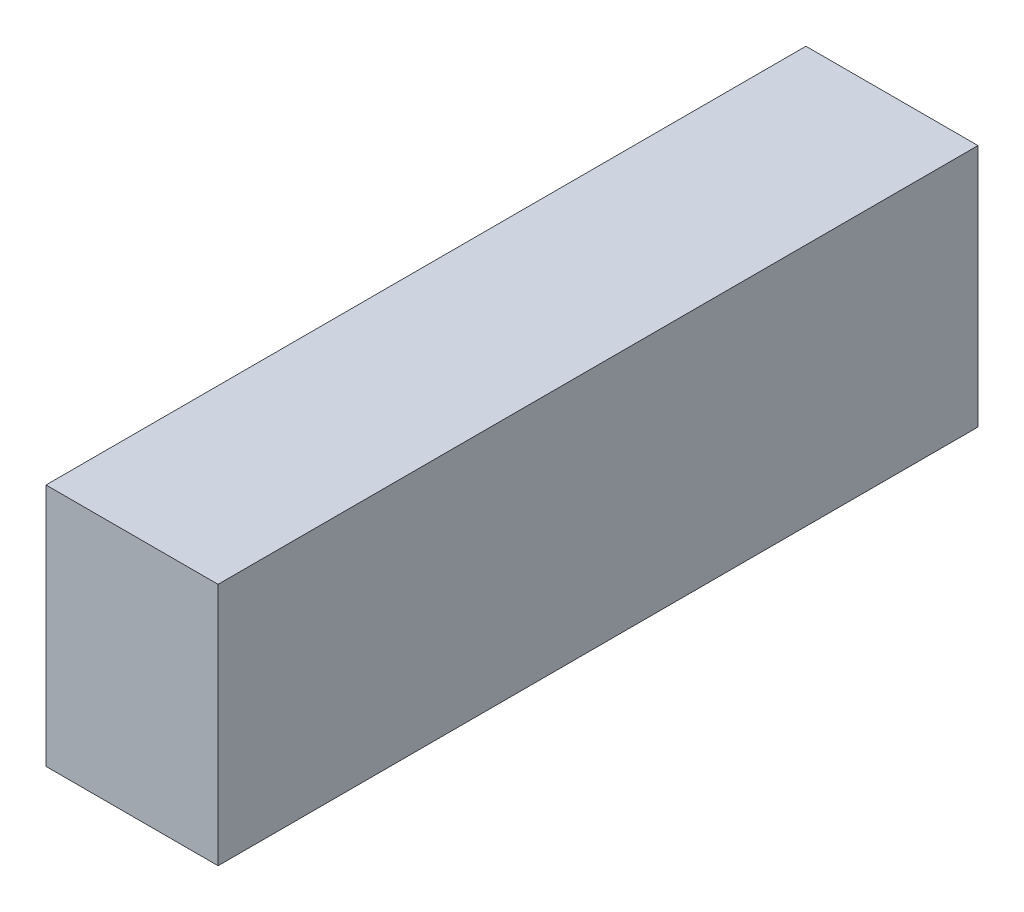
SolidWorks part; units mm, degrees
ref_plane "Front Plane" through (0, 0, 0) normal (0, 0, 1) x (1, 0, 0)
ref_plane "Top Plane" through (0, 0, 0) normal (0, 1, 0) x (1, 0, 0)
ref_plane "Right Plane" through (0, 0, 0) normal (1, 0, 0) x (0, 0, -1)
sketch "Case Sketch" plane through (0, 0, 0) normal (1, 0, 0) x (0, 0, -1)
  line L0 (53, 8) -> (53, 42)
  line L1 (53, 42) -> (-53, 42)
  line L2 (-53, 42) -> (-53, 8)
  line L3 (-53, 8) -> (53, 8)
extrude "Case" add sketch "Case Sketch" against normal blind 24
ref_axis "Engine Axis" through (1.2, 0, 0) along (-1, 0, 0)
